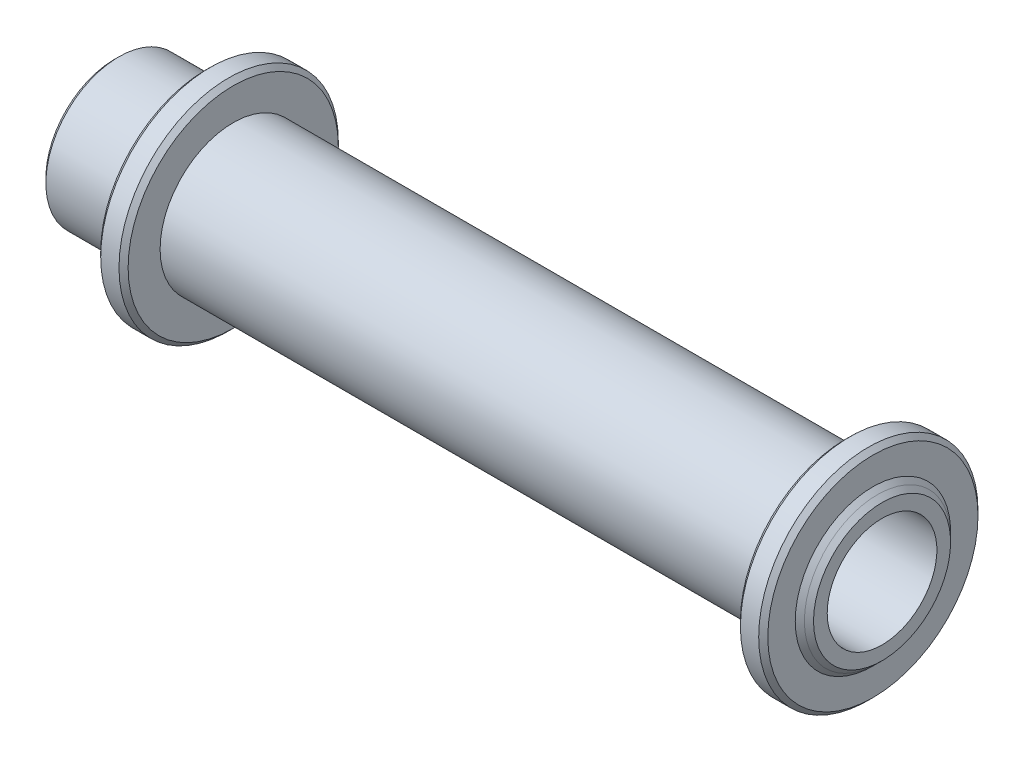
SolidWorks part; units mm, degrees
material "Plain Carbon Steel"
ref_plane "Front Plane" through (0, 0, 0) normal (0, 0, 1) x (1, 0, 0)
ref_plane "Top Plane" through (0, 0, 0) normal (0, 1, 0) x (1, 0, 0)
ref_plane "Right Plane" through (0, 0, 0) normal (1, 0, 0) x (0, 0, -1)
sketch "Sketch1" plane through (0, 0, 0) normal (0, 0, 1) x (1, 0, 0)
  line L0 (-123.6928, 0) -> (164.0502, 0) construction
  line L1 (-90.1166, 8) -> (-80.1166, 8)
  line L2 (-80.1166, 8) -> (-80.1166, 12)
  line L3 (-80.1166, 12) -> (-77.1166, 12)
  line L4 (-77.1166, 12) -> (-77.1166, 8)
  line L5 (-77.1166, 8) -> (-10.1166, 8)
  line L6 (-10.1166, 8) -> (-10.1166, 12)
  line L7 (-10.1166, 12) -> (-7.1166, 12)
  line L8 (-7.1166, 12) -> (-7.1166, 8)
  line L9 (-7.1166, 8) -> (-6.1166, 8)
  line L10 (-6.1166, 8) -> (-6.1166, 6)
  line L11 (-6.1166, 6) -> (-90.1166, 6)
  line L12 (-90.1166, 6) -> (-90.1166, 8)
  dimension "D1" = 8
  dimension "D2" = 6
  dimension "D3" = 84
  dimension "D4" = 3
  dimension "D5" = 3
  dimension "D6" = 4
  dimension "D7" = 4
  dimension "D8" = 4
  dimension "D9" = 4
  dimension "D10" = 13
  dimension "D11" = 4
revolve "Revolve1" add sketch "Sketch1" angle 360 about L0
chamfer "Chamfer1" distance 0.5 angle 45 8 edges at (-6.1166, 0, 8) (-7.1166, 0, 8) (-7.1166, 0, 12) (-77.1166, 0, 12) (-80.1166, 0, 12) (-80.1166, 0, 8) (-90.1166, 0, 8) (-10.1166, 0, 12)
